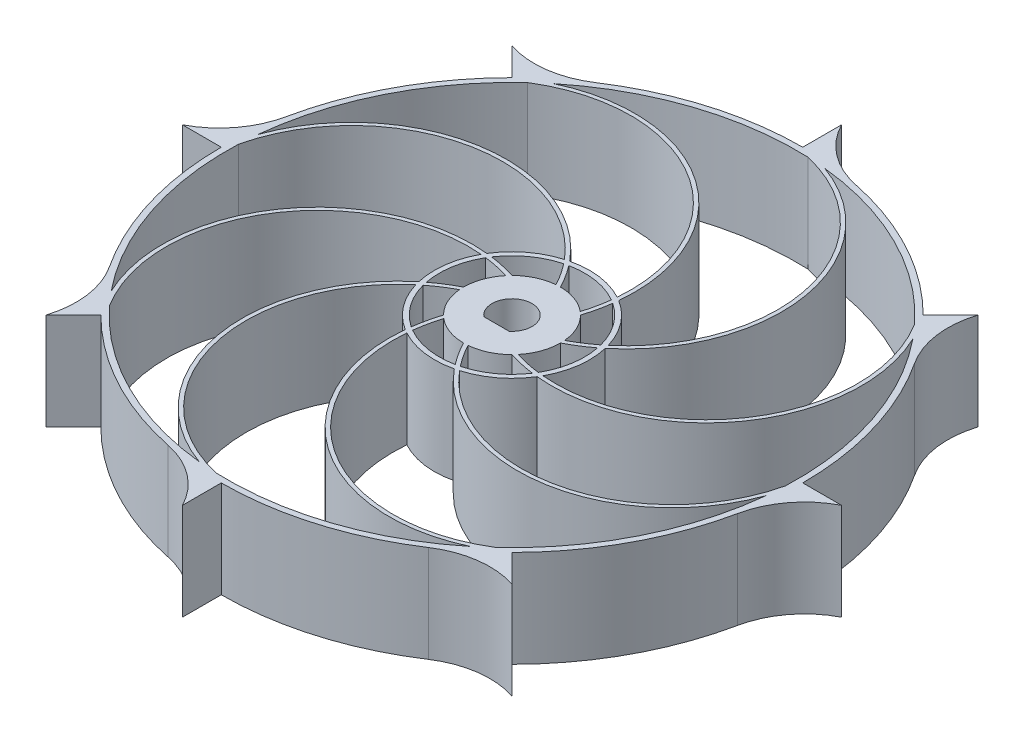
SolidWorks part; units mm, degrees
ref_plane "Front Plane" through (0, 0, 0) normal (0, 0, 1) x (1, 0, 0)
ref_plane "Top Plane" through (0, 0, 0) normal (0, 1, 0) x (1, 0, 0)
ref_plane "Right Plane" through (0, 0, 0) normal (1, 0, 0) x (0, 0, -1)
sketch "Sketch1" plane through (0, 0, 0) normal (0, 1, 0) x (1, 0, 0)
  line L0 (-2.603, -3.2) -> (2.603, -3.2)
  arc A0 (2.603, -3.2) -> (-2.603, -3.2) centre (0, 0) ccw
  circle A1 centre (0, 0) radius 60
  circle A28 centre (0, 0) radius 10
  circle A29 centre (0, 0) radius 58.8
  point P78 (0, 0)
  dimension "D1" = 8.25
  dimension "D2" = 120
  dimension "D3" = 20
  dimension "D7" = 3.2
  dimension "D4" = 1.2
extrude "Boss-Extrude1" add sketch "Sketch1" along normal blind 20 contours A1 A29 | A28 A0 L0 region at (-59.8303, 0, 0) region at (-9.7172, 0, 0)
sketch "Sketch4" plane through (0, 0, 0) normal (0, 1, 0) x (1, 0, 0)
  line L0 (-9.6325, -0.7106) -> (-10, 0)
  line L1 (0.1172, -59.2086) -> (0, -60)
  arc A0 (0, -60) -> (-10, 0) centre (4.6819, -28.3864) cw
  circle A1 centre (0, 0) radius 60 construction
  circle A2 centre (0, 0) radius 10 construction
  arc A3 (0.1172, -59.2086) -> (-9.6325, -0.7106) centre (4.6819, -28.3864) cw
  dimension "D1" = 0.8
extrude "Boss-Extrude4" add sketch "Sketch4" along normal up to surface (20 mm away) up to face at (0, 20, 58.8)
ref_axis "Axis1" through (0, 21, 0) along (0, -1, 0)
pattern_circular "CirPattern1" count 8 over 360 about axis through (0, 21, 0) along (0, -1, 0) of "Boss-Extrude4"
sketch "Sketch2" plane through (0, 0, 0) normal (0, 1, 0) x (1, 0, 0)
  circle A0 centre (0, 0) radius 15
  circle A1 centre (0, 0) radius 16
  dimension "D1" = 30
  dimension "D2" = 1
extrude "Boss-Extrude2" add sketch "Sketch2" along normal up to surface (20 mm away) up to face at (21.0377, 20, 26.1005)
sketch "Sketch3" plane through (0, 0, 0) normal (0, 1, 0) x (1, 0, 0)
  line L0 (0, -60) -> (0, -68)
  line L6 (-42.4264, -42.4264) -> (-48.0833, -48.0833)
  line L7 (-60, 0) -> (-68, 0)
  line L8 (-42.4264, 42.4264) -> (-48.0833, 48.0833)
  line L9 (0, 60) -> (0, 68)
  line L10 (42.4264, 42.4264) -> (48.0833, 48.0833)
  line L11 (60, 0) -> (68, 0)
  line L12 (42.4264, -42.4264) -> (48.0833, -48.0833)
  arc A0 (-48.0833, -48.0833) -> (-50.1745, -32.9017) centre (-65.1067, -42.6934) ccw
  arc A1 (0, -68) -> (-12.2137, -58.7437) centre (-15.8486, -76.2261) ccw
  arc A13 (-68, 0) -> (-58.7437, 12.2137) centre (-76.2261, 15.8486) ccw
  arc A15 (-48.0833, 48.0833) -> (-32.9017, 50.1745) centre (-42.6934, 65.1067) ccw
  circle A17 centre (0, 0) radius 60 construction
  circle A18 centre (0, 0) radius 60
  arc A19 (0, 68) -> (12.2137, 58.7437) centre (15.8486, 76.2261) ccw
  arc A20 (48.0833, 48.0833) -> (50.1745, 32.9017) centre (65.1067, 42.6934) ccw
  arc A21 (68, 0) -> (58.7437, -12.2137) centre (76.2261, -15.8486) ccw
  arc A22 (48.0833, -48.0833) -> (32.9017, -50.1745) centre (42.6934, -65.1067) ccw
  arc A23 (-58.7437, 12.2137) -> (-60, 0) centre (0, 0) ccw
  arc A24 (60, 0) -> (58.7437, -12.2137) centre (0, 0) cw
  point P30 (0, 0)
  point P33 (-2.1651, 1.25)
  point P42 (0, 0)
  dimension "D1" = 8
  dimension "D2" = 8
extrude "Boss-Extrude3" add sketch "Sketch3" along normal up to surface (20 mm away) contours A18 | A18 A1 L0 | A18 | A18 | A18 | A18 | A18 A13 L7 | A21 L11 A18 region at (-2.8725, 0, 62.1395) region at (41.9081, 0, 45.9704) region at (-45.9704, 0, 41.9081) region at (62.1395, 0, 2.8725) region at (-62.1395, 0, -2.8725) region at (45.9704, 0, -41.9081) region at (-41.9081, 0, -45.9704) region at (2.8725, 0, -62.1395) up to face at (-10.3369, 20, 6.247)
